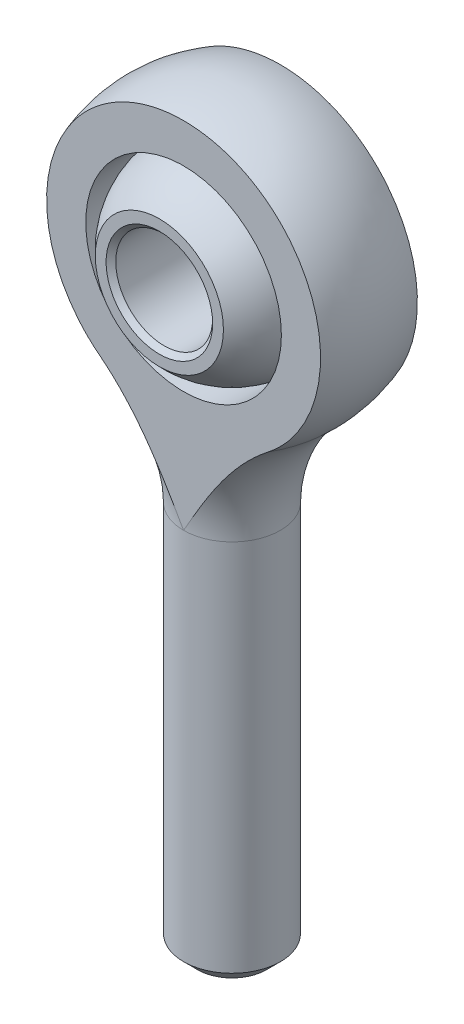
SolidWorks part; units mm, degrees
ref_plane "Front" through (0, 0, 0) normal (0, 0, 1) x (1, 0, 0)
ref_plane "Top" through (0, 0, 0) normal (0, 1, 0) x (1, 0, 0)
ref_plane "Right" through (0, 0, 0) normal (1, 0, 0) x (0, 0, -1)
sketch "Sketch1" plane through (0, 0, 0) normal (0, 0, 1) x (1, 0, 0)
  line L0 (0, 0) -> (0, -25.4)
  line L1 (0, -25.4) -> (3.175, -25.4)
  line L2 (3.175, -25.4) -> (3.175, 0)
  line L3 (3.175, 0) -> (0, 0)
  line L5 (0, 23.8125) -> (0, 0) construction
  line L6 (0, 23.8125) -> (9.525, 23.8125) construction
  line L7 (9.525, 23.8125) -> (9.525, 14.2875) construction
  line L8 (-3.175, -25.4) -> (-3.175, 0) construction
  arc A0 (6.3827, 7.2174) -> (0, 23.8125) centre (0, 14.2875) ccw construction
  circle A1 centre (0, 14.2875) radius 3.175 construction
  circle A2 centre (0, 14.2875) radius 6.35 construction
  circle A3 centre (0, 14.2875) radius 6.4135 construction
  arc A4 (3.175, 0) -> (6.3827, 7.2174) centre (12.8984, 0) cw construction
  dimension "A" = 6.35
  dimension "Ball Dia" = 12.7
  dimension "B" = 19.05
  dimension "D1" = 12.827
  dimension "D" = 39.6875
  dimension "E" = 25.4
  dimension "Thread Dia" = 6.35
revolve "Revolve1" add sketch "Sketch1" angle 360 about L5
chamfer "Chamfer2" distance 0.9071 angle 45 1 edges at (-3.175, -25.4, 0)
sketch "Sketch12" plane through (0, -25.4, 0) normal (0, -1, 0) x (1, 0, 0)
  circle A1 centre (0, 0) radius 2.2679
  circle A2 centre (0, 0) radius 2.2679
  dimension "D1" = 0
curve "Helix/Spiral1" pitch 0.9071 height 38.1 turns 42
sketch "Sketch13" plane through (0, 0, 0) normal (0, 0, 1) x (1, 0, 0)
  line L0 (3.175, -25.4) -> (3.175, -26.1938)
  line L1 (3.175, -26.1938) -> (2.5858, -25.8536)
  line L2 (2.5858, -25.8536) -> (2.5858, -25.7402)
  line L3 (2.5858, -25.7402) -> (3.175, -25.4)
  line L5 (2.8804, -25.5701) -> (2.8804, -26.0237) construction
  dimension "D1" = 0.1134
  dimension "D2" = 0.4536
  dimension "D3" = 60
sweep "Cut-Sweep2" [suppressed] cut profiles "Sketch13" path "Helix/Spiral1"
sketch "Sketch4" plane through (0, 0, 0) normal (0, 0, 1) x (1, 0, 0)
  line L0 (3.175, 0) -> (0, 0) construction
  line L2 (0, 23.8125) -> (0, 0) construction
  line L3 (3.175, 0) -> (0, 0)
  line L5 (0, 23.8125) -> (0, 0)
  line L6 (0, 23.8125) -> (0, 26.3525) construction
  arc A0 (6.3827, 7.2174) -> (0, 23.8125) centre (0, 14.2875) ccw construction
  arc A1 (6.3827, 7.2174) -> (0, 23.8125) centre (0, 14.2875) ccw
  arc A2 (6.3827, 7.2174) -> (3.175, 0) centre (12.8984, 0) ccw construction
  arc A3 (6.3827, 7.2174) -> (3.175, 0) centre (12.8984, 0) ccw
  dimension "D1" = 2.54
revolve "Revolve2" add sketch "Sketch4" angle 360 about L6
sketch "Sketch5" plane through (0, 0, 0) normal (1, 0, 0) x (0, 0, -1)
  line L0 (3.175, 23.8125) -> (9.525, 23.8125)
  line L1 (-3.175, 23.8125) -> (3.175, 23.8125) construction
  line L2 (-3.175, 23.8125) -> (-3.175, 1.27)
  line L3 (-3.175, 0) -> (3.175, 0) construction
  line L4 (3.175, 23.8125) -> (3.175, 1.27)
  line L5 (9.525, 23.8125) -> (9.525, 0)
  line L6 (9.525, 0) -> (3.175, 0)
  line L7 (-3.175, 0) -> (-9.525, 0)
  line L8 (-9.525, 0) -> (-9.525, 23.8125)
  line L9 (-9.525, 23.8125) -> (-3.175, 23.8125)
  line L10 (3.175, 0) -> (3.175, 1.27)
  line L11 (-3.175, 0) -> (-3.175, 1.27)
  line L12 (-3.175, 1.27) -> (3.175, 1.27) construction
  line L13 (0, 0) -> (0, 1.27) construction
  arc A0 (6.3827, 7.2174) -> (-6.3827, 7.2174) centre (0, 14.2875) ccw construction
  dimension "F" = 6.35
  dimension "D1" = 6.35
extrude "Cut-Extrude1" cut sketch "Sketch5" against normal through all and the other way through all
sketch "Sketch6" plane through (0, 0, 0) normal (0, 0, 1) x (1, 0, 0)
  circle A0 centre (0, 14.2875) radius 6.4135 construction
  circle A1 centre (0, 14.2875) radius 6.4135
extrude "Cut-Extrude2" cut sketch "Sketch6" against normal through all and the other way through all
sketch "Sketch7" plane through (0, 0, 0) normal (0, 0, 1) x (1, 0, 0)
  line L0 (0, 20.6375) -> (0, 7.9375)
  line L1 (0, 23.8125) -> (0, 0) construction
  line L2 (0, 0) -> (0, 7.9375) construction
  arc A0 (0, 7.9375) -> (0, 20.6375) centre (0, 14.2875) ccw
  circle A1 centre (0, 14.2875) radius 6.35 construction
revolve "Revolve3" add sketch "Sketch7" angle 360 about L2
sketch "Sketch8" plane through (0, 0, 0) normal (1, 0, 0) x (0, 0, -1)
  line L0 (-3.175, 23.8125) -> (3.175, 23.8125) construction
  line L1 (-4.7625, 23.8125) -> (4.7625, 23.8125) construction
  line L2 (-4.7625, 23.8125) -> (-4.7625, 0)
  line L3 (-4.7625, 0) -> (4.7625, 0) construction
  line L4 (4.7625, 23.8125) -> (4.7625, 0)
  line L5 (4.7625, 23.8125) -> (9.525, 23.8125)
  line L6 (9.525, 23.8125) -> (9.525, 0)
  line L7 (9.525, 0) -> (4.7625, 0)
  line L8 (-4.7625, 0) -> (-9.525, 0)
  line L9 (-9.525, 0) -> (-9.525, 23.8125)
  line L10 (-9.525, 23.8125) -> (-4.7625, 23.8125)
  dimension "C" = 9.525
extrude "Cut-Extrude3" cut sketch "Sketch8" against normal through all and the other way through all
sketch "Sketch10" plane through (0, 0, 0) normal (0, 0, 1) x (1, 0, 0)
  circle A0 centre (0, 14.2875) radius 3.175 construction
  circle A1 centre (0, 14.2875) radius 3.175
extrude "Cut-Extrude4" cut sketch "Sketch10" against normal through all and the other way through all
chamfer "Chamfer1" distance 0.3175 angle 45 2 edges at (3.175, 14.2875, -4.7625) (3.175, 14.2875, 4.7625)
sketch "Sketch11" plane through (0, 0, 0) normal (1, 0, 0) x (0, 0, -1)
  line L0 (0, 14.2875) -> (-4.7625, 15.4309) construction
  line L1 (3.175, 14.2875) -> (-3.175, 14.2875) construction
  line L2 (0, 14.2875) -> (-4.7625, 13.1441) construction
  line L3 (0, 23.8125) -> (0, 0) construction
  line L4 (-4.7625, 23.8125) -> (-4.7625, 0) construction
  line L5 (0, 14.2875) -> (0.0074, 14.2875) construction
  dimension "Swivel" = 27
equation "\"D1@Sketch1\"=\"Ball Dia@Sketch1\"*1.01"
equation "\"D1@Chamfer1\"=\"A@Sketch1\"/20"
equation "\"D1@Sketch5\"=\"Thread Dia@Sketch1\""
equation "\"D2@Sketch5\"=\"F@Sketch5\"/5"
equation "\"D1@Sketch13\" = \"D4@Helix/Spiral1\" * .125"
equation "\"D2@Sketch13\" = \"D4@Helix/Spiral1\" * .5"
equation "\"D1@Chamfer2\" = \"D4@Helix/Spiral1\" * 1"
equation "\"D3@Helix/Spiral1\" = \"E@Sketch1\" + .5"
